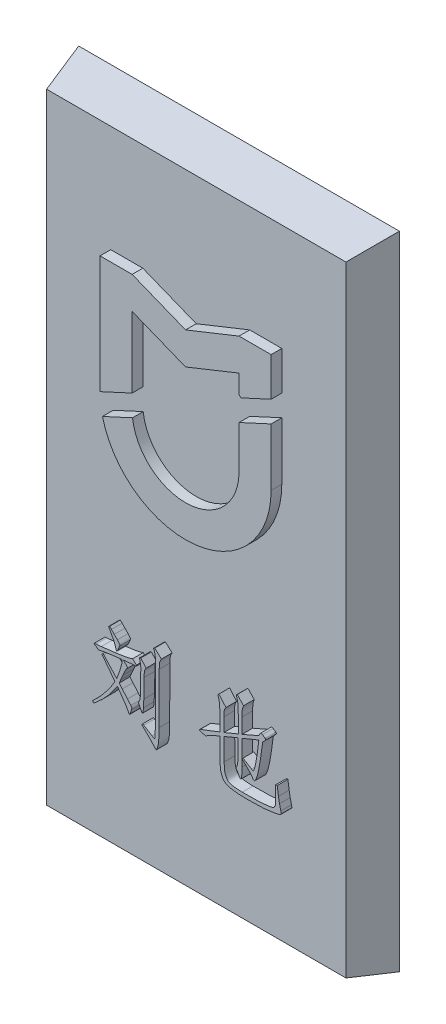
SolidWorks part; units mm, degrees
ref_plane "前视基准面" through (0, 0, 0) normal (0, 0, 1) x (1, 0, 0)
ref_plane "上视基准面" through (0, 0, 0) normal (0, 1, 0) x (1, 0, 0)
ref_plane "右视基准面" through (0, 0, 0) normal (1, 0, 0) x (0, 0, -1)
other "Configuration Table"
sketch "草图1" plane through (0, 0, 0) normal (0, 0, 1) x (1, 0, 0)
  line L18 (-15, -30) -> (15, -30)
  line L19 (-15, -30) -> (-15, 30)
  line L20 (-15, 30) -> (15, 30)
  line L21 (15, -30) -> (15, 30)
  line L22 (-15, -30) -> (15, 30) construction
  line L23 (-15, 30) -> (15, -30) construction
  point P0 (0, 0)
  dimension "D2" = 60
  dimension "D1" = 30
ref_plane "基准面1" through (0, 0, 4) normal (0, 0, 1) x (1, 0, 0)
sketch "草图2" plane through (0, 0, 4) normal (0, 0, 1) x (1, 0, 0)
  line L0 (-15, 30) -> (15, 30) construction
  line L1 (-14, -29) -> (14, -29)
  line L2 (-14, -29) -> (-14, 29)
  line L3 (-14, 29) -> (14, 29)
  line L4 (14, -29) -> (14, 29)
  line L5 (-14, -29) -> (14, 29) construction
  line L6 (-14, 29) -> (14, -29) construction
  line L7 (15, -30) -> (15, 30) construction
  point P0 (0, 0)
  dimension "D1" = 1
  dimension "D2" = 1
loft "放样1" add profiles "草图1", "草图2" connector at (-15, -30, 0) connector at (-14, -29, 4)
sketch "草图3" plane through (0, 0, 4) normal (0, 0, 1) x (1, 0, 0)
  line L0 (69.5095, 236.7647) -> (402.8428, 236.7647) construction
  line L1 (0, 3) -> (0, 0)
  line L2 (0, 0) -> (0, 41.0504) construction
  line L3 (-8, 8) -> (-8, 19)
  line L4 (-8, 19) -> (-5, 19)
  line L5 (-5, 19) -> (0, 17)
  line L6 (0, 17) -> (5, 19)
  line L7 (5, 19) -> (8, 19)
  line L8 (8, 19) -> (8, 15.3846)
  line L9 (8, 15.3846) -> (5, 14)
  line L10 (5, 14) -> (5, 16)
  line L11 (5, 16) -> (0, 14)
  line L12 (0, 14) -> (-5, 16)
  line L13 (-5, 16) -> (-5, 9.3846)
  line L14 (-5, 9.3846) -> (-8, 8)
  line L16 (5, 12) -> (8, 13.3846)
  line L19 (14, 29) -> (-14, 29) construction
  line L20 (8, 13.3846) -> (8, 8)
  line L21 (5, 12) -> (5, 8)
  line L22 (-4.964, 7.4012) -> (-7.7723, 6.1051)
  circle A0 centre (0, 8) radius 5
  circle A1 centre (0, 8) radius 8
  dimension "D1" = 5
  dimension "D2" = 15
  dimension "D3" = 2
  dimension "D4" = 3
  dimension "D5" = 2
  dimension "D6" = 3
  dimension "D7" = 6
extrude "凸台-拉伸2" add sketch "草图3" along normal blind 1 contours A1 L13 L12 L11 L10 L9 L8 L7 L6 L5 L4 L3 | L13 A1 L14 | A1 L16 L21 A0 L1 | A1 L20 L16 | L22 A1 L1 A0 | L11 A1 L12 region at (4.7825, 5.4619, 4) region at (-3.8597, 3.2925, 4) region at (7.5427, 11.7987, 4) region at (-6.2636, 10.7836, 4) region at (-0.9087, 16.3999, 4) region at (0, 15.168, 4)
sketch "草图4" plane through (0, 0, 4) normal (0, 0, 1) x (1, 0, 0)
  line L6 (-14, -17) -> (14, -17) construction
  line L7 (-14, -29) -> (-14, 29) construction
  line L8 (14, -29) -> (14, 29) construction
  text T0 "刘也" font "汉仪长仿宋体" height 6
  dimension "D1" = 17
extrude "凸台-拉伸3" add sketch "草图4" along normal blind 1
sketch "草图5" plane through (0, 0, 0) normal (0, 0, -1) x (-1, 0, 0)
  line L3 (15, -30) -> (-15, -30) construction
  line L4 (0, 18) -> (0, 0) construction
  line L5 (0, 0) -> (0, -18) construction
  circle A5 centre (0, 18) radius 5.5
  circle A6 centre (0, -18) radius 5.5
  circle A7 centre (0, 0) radius 5.5
  dimension "D5" = 12
  dimension "D1" = 11
extrude "切除-拉伸1" cut sketch "草图5" against normal blind 2
sketch "草图7" plane through (0, 0, 4) normal (0, 0, 1) x (1, 0, 0)
  line L0 (3.2108, -13.9623) -> (1.3838, -14.6693) construction
  line L1 (1.3838, -14.8163) -> (1.8889, -14.9544) construction
  line L2 (3.2223, -14.2896) -> (3.2338, -16.284) construction
  line L3 (8.9065, -17.5088) -> (8.7864, -16.9911) construction
  line L4 (8.7864, -16.9911) -> (8.6892, -16.4387) construction
  line L5 (8.6892, -16.4387) -> (8.569, -15.6192) construction
  line L6 (8.569, -15.6192) -> (8.4258, -15.6358) construction
  line L7 (8.4258, -15.6358) -> (8.413, -17.2071) construction
  line L8 (3.6072, -16.1882) -> (3.5944, -14.1349) construction
  line L9 (3.5944, -14.1349) -> (4.9163, -13.5826) construction
  line L10 (4.9163, -13.5826) -> (4.9163, -14.7997) construction
  line L11 (4.832, -16.3186) -> (4.9892, -16.6024) construction
  line L12 (5.2654, -15.7918) -> (5.2654, -13.4445) construction
  line L13 (5.2654, -13.4445) -> (6.8507, -12.7976) construction
  line L14 (6.1782, -15.4901) -> (5.3728, -14.9979) construction
  line L15 (5.3728, -14.9979) -> (5.3012, -15.127) construction
  line L16 (5.3012, -15.127) -> (5.6131, -15.4211) construction
  line L17 (5.6131, -15.4211) -> (5.9737, -15.7918) construction
  line L18 (5.9737, -15.7918) -> (6.2984, -16.1971) construction
  line L19 (7.4401, -12.3744) -> (7.1882, -12.1839) construction
  line L20 (7.0195, -12.1583) -> (6.8277, -12.4524) construction
  line L21 (6.8277, -12.4524) -> (5.2769, -13.1249) construction
  line L22 (5.2769, -13.1249) -> (5.2769, -11.7185) construction
  line L23 (5.4214, -10.7341) -> (4.832, -10.1127) construction
  line L24 (4.832, -10.1127) -> (4.7361, -10.1997) construction
  line L25 (4.9291, -11.753) -> (4.9291, -13.2629) construction
  line L26 (4.9291, -13.2629) -> (3.5829, -13.8242) construction
  line L27 (3.5829, -13.8242) -> (3.5829, -12.547) construction
  line L28 (3.7746, -11.7006) -> (3.1149, -10.9412) construction
  line L29 (3.1149, -10.9412) -> (3.0178, -11.0447) construction
  line L30 (3.2108, -12.3744) -> (3.2108, -13.9623) construction
  line L31 (-2.8861, -10.2163) -> (-2.9948, -10.2853) construction
  line L32 (-2.8017, -11.5459) -> (-2.826, -16.4822) construction
  line L33 (-3.138, -17.4488) -> (-3.9076, -16.9744) construction
  line L34 (-3.9076, -16.9744) -> (-4.0035, -16.9054) construction
  line L35 (-4.0035, -16.9054) -> (-4.0994, -17.0089) construction
  line L36 (-4.0994, -17.0089) -> (-3.9677, -17.1547) construction
  line L37 (-3.9677, -17.1547) -> (-3.3553, -17.7505) construction
  line L38 (-3.3553, -17.7505) -> (-2.9219, -18.2248) construction
  line L39 (-2.4898, -16.4643) -> (-2.4655, -11.7185) construction
  line L40 (-2.2609, -10.7954) -> (-2.8861, -10.2163) construction
  line L41 (-4.1838, -12.4434) -> (-4.1953, -12.8142) construction
  line L42 (-4.1953, -12.8142) -> (-4.2323, -14.6437) construction
  line L43 (-4.3525, -15.5323) -> (-4.2554, -15.7138) construction
  line L44 (-4.2554, -15.7138) -> (-4.148, -15.9209) construction
  line L45 (-3.9434, -15.5847) -> (-3.9076, -14.8598) construction
  line L46 (-3.9076, -14.8598) -> (-3.8718, -13.0814) construction
  line L47 (-3.6915, -12.2453) -> (-4.1953, -11.675) construction
  line L48 (-4.1953, -11.675) -> (-4.3154, -11.7275) construction
  line L49 (-8.702, -17.3887) -> (-8.6061, -17.5344) construction
  line L50 (-8.6061, -17.5344) -> (-8.4731, -17.4309) construction
  line L51 (-5.5658, -16.215) -> (-5.4214, -16.4822) construction
  line L52 (-5.4214, -16.4822) -> (-5.3255, -16.6638) construction
  line L53 (-5.1695, -16.6638) -> (-5.0608, -16.2917) construction
  line L54 (-5.1209, -15.9734) -> (-5.4341, -15.6103) construction
  line L55 (-5.4341, -15.6103) -> (-5.9264, -15.049) construction
  line L56 (-5.9264, -15.049) -> (-6.214, -14.7128) construction
  line L57 (-6.214, -14.7128) -> (-6.0823, -14.411) construction
  line L58 (-6.0823, -14.411) -> (-5.8535, -13.8932) construction
  line L59 (-5.4098, -13.0993) -> (-5.7934, -12.6505) construction
  line L60 (-5.7934, -12.6505) -> (-5.1938, -12.5905) construction
  line L61 (-5.1938, -12.5905) -> (-4.6287, -12.547) construction
  line L62 (-4.5929, -12.4434) -> (-4.9649, -12.1238) construction
  line L63 (-7.885, -12.5905) -> (-8.3657, -12.625) construction
  line L64 (-8.4859, -12.7452) -> (-8.2328, -12.9356) construction
  line L65 (-8.2328, -12.9356) -> (-8.1612, -12.9957) construction
  line L66 (-8.1612, -12.9957) -> (-7.9566, -12.9523) construction
  line L67 (-7.9566, -12.9523) -> (-7.4516, -12.8577) construction
  line L68 (-7.4516, -12.8577) -> (-6.9722, -12.7886) construction
  line L69 (-6.9722, -12.7886) -> (-5.9506, -12.6672) construction
  line L70 (-5.9506, -12.6672) -> (-5.9506, -12.8577) construction
  line L71 (-7.6447, -13.1594) -> (-7.729, -13.0737) construction
  line L72 (-7.729, -13.0737) -> (-7.8249, -13.1773) construction
  line L73 (-7.8249, -13.1773) -> (-7.729, -13.3064) construction
  line L74 (-8.6176, -17.3017) -> (-8.702, -17.3887) construction
  line L75 (-7.2113, -10.6305) -> (-7.1154, -10.7775) construction
  line L76 (-6.9722, -11.0537) -> (-6.8034, -11.3554) construction
  line L77 (-6.5273, -12.0292) -> (-6.503, -12.1149) construction
  line L78 (-6.3112, -12.0292) -> (-6.191, -11.7185) construction
  line L79 (-6.3828, -11.2953) -> (-6.6717, -10.9936) construction
  line L80 (-6.6717, -10.9936) -> (-6.9351, -10.7264) construction
  line L81 (-6.9351, -10.7264) -> (-7.1039, -10.5538) construction
  line L82 (-7.1039, -10.5538) -> (-7.2113, -10.6305) construction
  line L83 (3.2108, -13.9623) -> (1.3838, -14.6693)
  line L84 (1.3838, -14.8163) -> (1.8889, -14.9544)
  line L85 (3.2223, -14.2896) -> (3.2338, -16.284)
  line L86 (8.9065, -17.5088) -> (8.7864, -16.9911)
  line L87 (8.7864, -16.9911) -> (8.6892, -16.4387)
  line L88 (8.6892, -16.4387) -> (8.569, -15.6192)
  line L89 (8.569, -15.6192) -> (8.4258, -15.6358)
  line L90 (8.4258, -15.6358) -> (8.413, -17.2071)
  line L91 (3.6072, -16.1882) -> (3.5944, -14.1349)
  line L92 (3.5944, -14.1349) -> (4.9163, -13.5826)
  line L93 (4.9163, -13.5826) -> (4.9163, -14.7997)
  line L94 (4.832, -16.3186) -> (4.9892, -16.6024)
  line L95 (5.2654, -15.7918) -> (5.2654, -13.4445)
  line L96 (5.2654, -13.4445) -> (6.8507, -12.7976)
  line L97 (6.1782, -15.4901) -> (5.3728, -14.9979)
  line L98 (5.3728, -14.9979) -> (5.3012, -15.127)
  line L99 (5.3012, -15.127) -> (5.6131, -15.4211)
  line L100 (5.6131, -15.4211) -> (5.9737, -15.7918)
  line L101 (5.9737, -15.7918) -> (6.2984, -16.1971)
  line L102 (7.4401, -12.3744) -> (7.1882, -12.1839)
  line L103 (7.0195, -12.1583) -> (6.8277, -12.4524)
  line L104 (6.8277, -12.4524) -> (5.2769, -13.1249)
  line L105 (5.2769, -13.1249) -> (5.2769, -11.7185)
  line L106 (5.4214, -10.7341) -> (4.832, -10.1127)
  line L107 (4.832, -10.1127) -> (4.7361, -10.1997)
  line L108 (4.9291, -11.753) -> (4.9291, -13.2629)
  line L109 (4.9291, -13.2629) -> (3.5829, -13.8242)
  line L110 (3.5829, -13.8242) -> (3.5829, -12.547)
  line L111 (3.7746, -11.7006) -> (3.1149, -10.9412)
  line L112 (3.1149, -10.9412) -> (3.0178, -11.0447)
  line L113 (3.2108, -12.3744) -> (3.2108, -13.9623)
  line L114 (-2.8861, -10.2163) -> (-2.9948, -10.2853)
  line L115 (-2.8017, -11.5459) -> (-2.826, -16.4822)
  line L116 (-3.138, -17.4488) -> (-3.9076, -16.9744)
  line L117 (-3.9076, -16.9744) -> (-4.0035, -16.9054)
  line L118 (-4.0035, -16.9054) -> (-4.0994, -17.0089)
  line L119 (-4.0994, -17.0089) -> (-3.9677, -17.1547)
  line L120 (-3.9677, -17.1547) -> (-3.3553, -17.7505)
  line L121 (-3.3553, -17.7505) -> (-2.9219, -18.2248)
  line L122 (-2.4898, -16.4643) -> (-2.4655, -11.7185)
  line L123 (-2.2609, -10.7954) -> (-2.8861, -10.2163)
  line L124 (-4.1838, -12.4434) -> (-4.1953, -12.8142)
  line L125 (-4.1953, -12.8142) -> (-4.2323, -14.6437)
  line L126 (-4.3525, -15.5323) -> (-4.2554, -15.7138)
  line L127 (-4.2554, -15.7138) -> (-4.148, -15.9209)
  line L128 (-3.9434, -15.5847) -> (-3.9076, -14.8598)
  line L129 (-3.9076, -14.8598) -> (-3.8718, -13.0814)
  line L130 (-3.6915, -12.2453) -> (-4.1953, -11.675)
  line L131 (-4.1953, -11.675) -> (-4.3154, -11.7275)
  line L132 (-8.702, -17.3887) -> (-8.6061, -17.5344)
  line L133 (-8.6061, -17.5344) -> (-8.4731, -17.4309)
  line L134 (-5.5658, -16.215) -> (-5.4214, -16.4822)
  line L135 (-5.4214, -16.4822) -> (-5.3255, -16.6638)
  line L136 (-5.1695, -16.6638) -> (-5.0608, -16.2917)
  line L137 (-5.1209, -15.9734) -> (-5.4341, -15.6103)
  line L138 (-5.4341, -15.6103) -> (-5.9264, -15.049)
  line L139 (-5.9264, -15.049) -> (-6.214, -14.7128)
  line L140 (-6.214, -14.7128) -> (-6.0823, -14.411)
  line L141 (-6.0823, -14.411) -> (-5.8535, -13.8932)
  line L142 (-5.4098, -13.0993) -> (-5.7934, -12.6505)
  line L143 (-5.7934, -12.6505) -> (-5.1938, -12.5905)
  line L144 (-5.1938, -12.5905) -> (-4.6287, -12.547)
  line L145 (-4.5929, -12.4434) -> (-4.9649, -12.1238)
  line L146 (-7.885, -12.5905) -> (-8.3657, -12.625)
  line L147 (-8.4859, -12.7452) -> (-8.2328, -12.9356)
  line L148 (-8.2328, -12.9356) -> (-8.1612, -12.9957)
  line L149 (-8.1612, -12.9957) -> (-7.9566, -12.9523)
  line L150 (-7.9566, -12.9523) -> (-7.4516, -12.8577)
  line L151 (-7.4516, -12.8577) -> (-6.9722, -12.7886)
  line L152 (-6.9722, -12.7886) -> (-5.9506, -12.6672)
  line L153 (-5.9506, -12.6672) -> (-5.9506, -12.8577)
  line L154 (-7.6447, -13.1594) -> (-7.729, -13.0737)
  line L155 (-7.729, -13.0737) -> (-7.8249, -13.1773)
  line L156 (-7.8249, -13.1773) -> (-7.729, -13.3064)
  line L157 (-8.6176, -17.3017) -> (-8.702, -17.3887)
  line L158 (-7.2113, -10.6305) -> (-7.1154, -10.7775)
  line L159 (-6.9722, -11.0537) -> (-6.8034, -11.3554)
  line L160 (-6.5273, -12.0292) -> (-6.503, -12.1149)
  line L161 (-6.3112, -12.0292) -> (-6.191, -11.7185)
  line L162 (-6.3828, -11.2953) -> (-6.6717, -10.9936)
  line L163 (-6.6717, -10.9936) -> (-6.9351, -10.7264)
  line L164 (-6.9351, -10.7264) -> (-7.1039, -10.5538)
  line L165 (-7.1039, -10.5538) -> (-7.2113, -10.6305)
  spline S0 degree 3 poles (-1033.717, 1696.6076) (14.5849, -31.3392) (2.3796, -13.84) (1.322, -14.7057) (1.3032, -14.7272) (1.2978, -14.7519) (1.3028, -14.776) (1.3219, -14.7941) (2.4833, -15.4174) (10.8456, 3.4261) (-689.6183, -1891.6231) knots -16.626684 -16.626684 -16.626684 -16.626684 0.172084 0.308952 0.423314 0.521848 0.615174 0.717267 0.839241 17.04599 17.04599 17.04599 17.04599 only from (1.3838, -14.6693) to (1.3838, -14.8163) construction
  spline S1 degree 3 poles (-1193.4267, 1588.4483) (4.6942, -35.4098) (-2.0793, -17.6856) (2.0886, -14.8069) (2.1786, -14.7467) (2.255, -14.7057) (2.3236, -14.6723) (2.394, -14.6406) (2.4842, -14.6016) (2.5935, -14.5536) (2.723, -14.4991) (2.8716, -14.4348) (21.1798, -6.8784) (36.675, 7.0863) (846.5091, -1827.4773) knots -9.913111 -9.913111 -9.913111 -9.913111 0.088354 0.168711 0.240996 0.305231 0.342298 0.393919 0.460114 0.539323 0.633116 0.74183 0.864014 40.342075 40.342075 40.342075 40.342075 only from (1.8889, -14.9544) to (3.2223, -14.2896) construction
  spline S2 degree 3 poles (-1996.6425, -26.0924) (21.1619, -1.4114) (2.9373, -9.1514) (3.2408, -16.6481) (3.2493, -16.8011) (3.2608, -16.9395) (3.287, -17.0743) (3.3282, -17.2177) (3.3889, -17.3745) (3.4475, -17.514) (3.5093, -17.6275) (3.5725, -17.7068) (3.6497, -17.778) (3.7401, -17.842) (3.8439, -17.8993) (3.961, -17.9489) (4.091, -17.9913) (4.2346, -18.0246) (4.3907, -18.0542) (4.5598, -18.0774) (4.7413, -18.0999) (4.9353, -18.1162) (5.1417, -18.1268) (5.3603, -18.1366) (17.0583, -18.3013) (28.6468, -3.9526) (45.2697, -2017.6338) knots -5.726077 -5.726077 -5.726077 -5.726077 0.051298 0.096629 0.136668 0.171139 0.205044 0.243843 0.287585 0.336355 0.362012 0.388335 0.415202 0.443856 0.474721 0.507699 0.543092 0.581467 0.622821 0.667242 0.714879 0.765695 0.819407 0.876414 0.936712 9.962298 9.962298 9.962298 9.962298 only from (3.2338, -16.284) to (5.8305, -18.1391) construction
  spline S3 degree 3 poles (-13.558, -2017.9262) (-16.1126, -3.2156) (-4.8916, -18.3162) (6.2967, -18.1363) (6.5077, -18.135) (6.702, -18.1289) (6.8797, -18.1244) (7.0413, -18.1179) (7.1862, -18.1106) (7.3593, -18.0983) (7.5693, -18.079) (7.8251, -18.0454) (8.0919, -18.0098) (8.3171, -17.9718) (8.4924, -17.939) (8.6085, -17.9125) (8.7077, -17.8849) (8.7894, -17.8553) (8.8564, -17.8272) (8.9046, -17.795) (9.7801, -17.0547) (-10.3073, -3.2872) (1708.116, -1071.7951) knots -10.275083 -10.275083 -10.275083 -10.275083 0.076298 0.147407 0.213324 0.274064 0.329613 0.379985 0.425587 0.465631 0.542665 0.62318 0.707468 0.794943 0.837249 0.874555 0.906545 0.933712 0.95606 0.97423 0.988354 1.993762 1.993762 1.993762 1.993762 only from (5.8305, -18.1391) to (8.9538, -17.7249) construction
  spline S4 degree 3 poles (1950.4824, 462.1548) (-3.6389, -24.2841) (9.4886, -19.2587) (8.928, -17.6283) (8.3828, -15.5017) (24.8318, -10.629) (-1966.0478, -332.6785) knots -22.527171 -22.527171 -22.527171 -22.527171 0.152758 0.441236 0.761695 29.779876 29.779876 29.779876 29.779876 only from (8.9538, -17.7249) to (8.9065, -17.5088) construction
  spline S5 degree 3 poles (1964.363, -433.7342) (-12.5579, -7.9686) (9.2006, -15.0961) (8.374, -17.3632) (8.3303, -17.4427) (8.2869, -17.5147) (8.228, -17.5691) (8.157, -17.6037) (8.0635, -17.637) (7.9458, -17.6647) (7.8043, -17.6919) (7.6382, -17.714) (7.4476, -17.7331) (7.1586, -17.7525) (6.7742, -17.7729) (6.2972, -17.7876) (-12.0936, -18.089) (-30.4237, 1.2715) (-38.3924, -2017.04) knots -2.060584 -2.060584 -2.060584 -2.060584 0.022746 0.046909 0.073942 0.103777 0.121266 0.144564 0.173661 0.209707 0.252274 0.302159 0.35908 0.423101 0.560508 0.702361 0.848718 16.964876 16.964876 16.964876 16.964876 only from (8.413, -17.2071) to (5.3012, -17.7939) construction
  spline S6 degree 3 poles (-46.7827, -2016.9641) (22.8077, 5.2469) (13.3561, -18.3583) (4.7621, -17.7744) (4.5344, -17.7516) (4.3394, -17.7124) (4.1743, -17.6679) (4.0418, -17.6087) (3.9373, -17.5417) (3.8494, -17.4317) (3.7799, -17.2879) (3.7089, -17.1204) (3.6584, -16.9548) (3.628, -16.7397) (3.0291, -6.34) (22.0683, 4.4844) (-1996.1462, -34.556) knots -8.866171 -8.866171 -8.866171 -8.866171 0.102703 0.194721 0.275299 0.345385 0.405658 0.456275 0.49919 0.535795 0.603996 0.668093 0.728927 0.787086 0.898182 11.780137 11.780137 11.780137 11.780137 only from (5.3012, -17.7939) to (3.6072, -16.1882) construction
  spline S7 degree 3 poles (2004.3322, 28.2132) (-5.4357, 8.8885) (4.9939, -3.0766) (4.9157, -15.1159) (4.913, -15.2229) (4.9105, -15.3009) (4.9062, -15.3675) (4.8976, -15.4411) (4.8881, -15.5311) (4.8742, -15.6326) (4.8595, -15.7344) (4.8403, -15.8267) (4.8184, -15.904) (4.7924, -15.9663) (4.7664, -16.0149) (4.7485, -16.0553) (4.7377, -16.0864) (4.7267, -16.1124) (4.7369, -16.1442) (4.7545, -16.1874) (8.4419, -22.4311) (7.4888, -21.5343) (1094.0182, -1693.6924) knots -22.721442 -22.721442 -22.721442 -22.721442 0.117235 0.209236 0.277643 0.321637 0.358354 0.405016 0.463185 0.53135 0.600551 0.659631 0.71141 0.753745 0.788334 0.81677 0.837638 0.852065 0.86867 0.898605 0.942334 14.623876 14.623876 14.623876 14.623876 only from (4.9163, -14.7997) to (4.832, -16.3186) construction
  spline S8 degree 3 poles (-1550.7197, -1273.4139) (19.3456, 2.9931) (3.2309, -14.1918) (5.0799, -16.7505) (5.7712, -17.6613) (19.4263, 1.9782) (-1061.0354, -1708.7198) knots -34.275912 -34.275912 -34.275912 -34.275912 0.381659 0.667499 0.869536 12.383747 12.383747 12.383747 12.383747 only from (4.9892, -16.6024) to (5.1567, -16.8095) construction
  spline S9 degree 3 poles (918.7555, -1795.635) (-5.5243, 1.4675) (4.8071, -17.3305) (5.1958, -16.7827) (5.2129, -16.7483) (5.2282, -16.7063) (5.2394, -16.6557) (5.2459, -16.5944) (5.2522, -16.5121) (5.257, -16.4089) (5.2608, -16.2845) (5.2627, -16.1391) (5.4392, -7.5851) (-9.7444, 1.0472) (2005.1553, -7.1429) knots -1.687714 -1.687714 -1.687714 -1.687714 0.017456 0.042472 0.079552 0.130072 0.168818 0.227795 0.306061 0.404936 0.523255 0.662264 0.820778 24.999128 24.999128 24.999128 24.999128 only from (5.1567, -16.8095) to (5.2654, -15.7918) construction
  spline S10 degree 3 poles (1999.4433, -182.4933) (-0.9536, 17.1275) (8.3501, 1.4035) (6.8086, -13.2123) (6.7917, -13.371) (6.7732, -13.5025) (6.7549, -13.6268) (6.7362, -13.7638) (6.7125, -13.9226) (6.6791, -14.1669) (6.6279, -14.4944) (6.5596, -14.8224) (6.5056, -15.0718) (6.4665, -15.2245) (6.4351, -15.3421) (6.405, -15.4266) (6.3778, -15.4844) (6.3562, -15.5253) (6.3378, -15.5519) (6.3166, -15.5656) (6.2921, -15.5599) (6.2639, -15.5443) (4.0424, -14.2877) (11.2127, 0.4883) (-1139.8748, -1654.3969) knots -14.529546 -14.529546 -14.529546 -14.529546 0.077669 0.143357 0.196643 0.237586 0.276416 0.322552 0.376056 0.437289 0.569617 0.708128 0.772877 0.82528 0.866104 0.894742 0.914992 0.930089 0.941025 0.94733 0.953792 0.964678 0.979985 3.500837 3.500837 3.500837 3.500837 only from (6.8507, -12.7976) to (6.1782, -15.4901) construction
  spline S11 degree 3 poles (-1459.7871, -1376.4789) (16.124, -1.0165) (4.8212, -14.6345) (6.361, -16.2729) (7.1105, -16.8641) (15.6434, 1.6427) (-747.2579, -1868.7131) knots -40.720986 -40.720986 -40.720986 -40.720986 0.346655 0.629517 0.83833 17.401909 17.401909 17.401909 17.401909 only from (6.2984, -16.1971) to (6.4186, -16.3007) construction
  spline S12 degree 3 poles (837.9651, -1835.1249) (-8.1419, 10.6055) (5.776, -17.2113) (6.5025, -16.2565) (6.528, -16.2095) (6.5563, -16.1512) (6.5901, -16.0734) (6.631, -15.9775) (6.6736, -15.8661) (6.7146, -15.7421) (6.7515, -15.6071) (6.7856, -15.4601) (6.8204, -15.2999) (6.8542, -15.124) (6.8917, -14.9328) (6.9306, -14.7215) (6.9732, -14.4828) (7.0122, -14.2083) (7.0571, -13.8958) (7.0902, -13.6158) (7.1179, -13.389) (7.1385, -13.2361) (7.1567, -13.1048) (7.1715, -12.9952) (7.1853, -12.9069) (7.1977, -12.8407) (7.2081, -12.7966) (7.217, -12.763) (7.2413, -12.7362) (7.2737, -12.7029) (7.3166, -12.6607) (7.3686, -12.617) (7.4169, -12.5708) (7.4586, -12.5329) (7.4821, -12.4989) (7.4993, -12.4634) (7.0362, -10.9223) (-17.6107, -31.0912) (1493.2118, 1326.3414) knots -0.749252 -0.749252 -0.749252 -0.749252 0.011116 0.024256 0.034759 0.050015 0.070334 0.09545 0.124469 0.15558 0.188759 0.224443 0.263394 0.305925 0.352459 0.40264 0.459525 0.525733 0.60077 0.685168 0.727217 0.76409 0.795449 0.821898 0.843179 0.859308 0.869947 0.875726 0.883767 0.895184 0.909185 0.926664 0.943691 0.957044 0.966676 0.973237 0.984469 2.007557 2.007557 2.007557 2.007557 only from (6.4186, -16.3007) to (7.4401, -12.3744) construction
  spline S13 degree 3 poles (902.0496, 1776.4099) (0.6886, -34.6242) (9.0767, -12.9356) (7.086, -12.1281) (6.1315, -12.1467) (19.65, -37.5566) (-984.4161, 1724.6464) knots -32.736634 -32.736634 -32.736634 -32.736634 0.367152 0.634154 0.821366 13.935133 13.935133 13.935133 13.935133 only from (7.1882, -12.1839) to (7.0195, -12.1583) construction
  spline S14 degree 3 poles (-1994.6009, 0.495) (23.7054, -26.4113) (4.9761, -18.7485) (5.2835, -11.3643) (5.2914, -11.232) (5.3038, -11.1262) (5.3257, -11.034) (5.3512, -10.9406) (6.9792, -5.8121) (22.7426, -5.6507) (-1877.5534, 663.1337) knots -21.608795 -21.608795 -21.608795 -21.608795 0.198899 0.364768 0.496393 0.59539 0.682927 0.77943 0.885076 16.774062 16.774062 16.774062 16.774062 only from (5.2769, -11.7185) to (5.4214, -10.7341) construction
  spline S15 degree 3 poles (1902.8334, 619.7227) (-16.1551, -6.6372) (3.4236, -5.5784) (4.816, -10.4468) (4.8463, -10.5591) (4.8758, -10.7012) (4.902, -10.8854) (4.9158, -11.0799) (4.9214, -11.254) (4.9279, -11.4048) (4.905, -22.6176) (16.3078, -33.5295) (-1993.4919, -88.7053) knots -9.399112 -9.399112 -9.399112 -9.399112 0.086759 0.167144 0.240968 0.308143 0.443474 0.594867 0.67934 0.775169 0.882309 22.030604 22.030604 22.030604 22.030604 only from (4.7361, -10.1997) to (4.9291, -11.753) construction
  spline S16 degree 3 poles (-1996.3066, -6.3279) (21.0986, -26.1786) (3.2376, -19.0978) (3.5925, -12.2086) (3.6071, -12.0674) (3.6279, -11.9648) (3.6579, -11.8939) (3.6875, -11.8361) (6.3076, -7.6291) (19.1276, -10.4641) (-1635.6374, 1133.6983) knots -22.753125 -22.753125 -22.753125 -22.753125 0.200316 0.389353 0.554689 0.680516 0.74126 0.814082 0.900083 17.48624 17.48624 17.48624 17.48624 only from (3.5829, -12.547) to (3.7746, -11.7006) construction
  spline S17 degree 3 poles (1903.9912, 610.2623) (-20.7158, -5.6325) (1.4769, -5.2348) (3.1267, -11.4022) (3.1599, -11.5753) (3.1876, -11.7958) (3.8456, -21.4883) (-18.235, -31.7664) (2002.9406, 15.7492) knots -13.754831 -13.754831 -13.754831 -13.754831 0.142454 0.27858 0.408689 0.533703 0.771853 21.965234 21.965234 21.965234 21.965234 only from (3.0178, -11.0447) to (3.2108, -12.3744) construction
  spline S18 degree 3 poles (1863.0803, 709.0915) (-22.3797, -4.1401) (-5.0305, -4.4694) (-2.8997, -10.5404) (-2.8683, -10.6465) (-2.844, -10.7698) (-2.829, -10.9212) (-2.8225, -11.0733) (-2.8168, -11.193) (-2.8154, -11.2703) (-2.8106, -11.3328) (-2.8079, -11.3968) (-2.5223, -14.669) (-19.2275, -18.627) (1995.8178, 61.3832) knots -14.7087 -14.7087 -14.7087 -14.7087 0.116167 0.216181 0.30306 0.374052 0.509134 0.657525 0.72919 0.788892 0.837713 0.875556 0.938334 8.497053 8.497053 8.497053 8.497053 only from (-2.9948, -10.2853) to (-2.8017, -11.5459) construction
  spline S19 degree 3 poles (1996.6884, -57.1725) (-15.54, -4.2723) (-2.5643, -10.6635) (-2.8326, -16.6987) (-2.8349, -16.7929) (-2.8368, -16.8769) (-2.8416, -16.9497) (-2.8431, -17.0124) (-2.8477, -17.0639) (-2.8518, -17.1377) (-2.8594, -17.2275) (-2.8586, -17.3285) (-2.6706, -19.1698) (-24.0229, -19.8512) (1993.9836, -127.1361) knots -18.086944 -18.086944 -18.086944 -18.086944 0.116901 0.223456 0.319585 0.404033 0.479451 0.541837 0.595221 0.636857 0.766948 0.869544 0.944906 6.362298 6.362298 6.362298 6.362298 only from (-2.826, -16.4822) to (-2.8618, -17.4654) construction
  spline S20 degree 3 poles (1920.7346, -564.8783) (-19.9028, -9.0246) (-2.2232, -15.9139) (-2.8844, -17.541) (-2.8944, -17.5636) (-2.9124, -17.5786) (-2.943, -17.5624) (-2.9871, -17.5419) (-7.9881, -14.4729) (-0.924, -15.4233) (-1899.5268, 617.8288) knots -13.418067 -13.418067 -13.418067 -13.418067 0.123946 0.216991 0.278308 0.31908 0.381479 0.515917 0.721003 45.525651 45.525651 45.525651 45.525651 only from (-2.8618, -17.4654) to (-3.138, -17.4488) construction
  spline S21 degree 3 poles (194.9213, -2008.3902) (-15.0275, 1.5883) (-8.4676, -12.6222) (-2.8057, -18.3428) (-2.0182, -19.0945) (7.0662, -6.6445) (-1066.911, -1711.4586) knots -97.933846 -97.933846 -97.933846 -97.933846 0.408799 0.710783 0.906834 13.513962 13.513962 13.513962 13.513962 only from (-2.9219, -18.2248) to (-2.7416, -18.3897) construction
  spline S22 degree 3 poles (1541.3019, -1289.3663) (-17.2182, -8.6749) (-3.0151, -19.2135) (-2.6957, -18.315) (-2.6594, -18.2339) (-2.6181, -18.1202) (-2.5776, -17.9866) (-2.5431, -17.8417) (-2.5239, -17.6904) (-2.5098, -17.4826) (-2.5022, -17.2234) (-2.497, -16.9689) (-2.4939, -16.7788) (-2.491, -16.6565) (-2.4063, -10.64) (-11.8864, -4.6267) (1997.4337, -6.5983) knots -1.306783 -1.306783 -1.306783 -1.306783 0.011073 0.038994 0.08476 0.148534 0.222584 0.297979 0.375406 0.454948 0.615659 0.771094 0.84328 0.905715 0.957736 10.02345 10.02345 10.02345 10.02345 only from (-2.7416, -18.3897) to (-2.4898, -16.4643) construction
  spline S23 degree 3 poles (-2002.0433, 23.4082) (17.2178, -26.8655) (-2.9385, -18.8244) (-2.4518, -11.3454) (-2.4395, -11.2317) (-2.4299, -11.1629) (-2.4183, -11.1079) (-2.4062, -11.0612) (-2.3851, -11.014) (-2.3537, -10.9557) (0.2121, -6.3458) (14.755, -8.7652) (-1720.7414, 1012.1287) knots -22.788299 -22.788299 -22.788299 -22.788299 0.226747 0.424712 0.510059 0.582424 0.640662 0.684729 0.732249 0.801029 0.890645 17.139984 17.139984 17.139984 17.139984 only from (-2.4655, -11.7185) to (-2.2609, -10.7954) construction
  spline S24 degree 3 poles (1924.5555, 516.4873) (-21.4595, -4.1063) (-5.6484, -6.1098) (-4.2553, -11.9618) (-4.2351, -12.066) (-4.2157, -12.1849) (-3.2666, -19.1695) (-14.338, -27.5253) (1984.5585, 198.7689) knots -24.265145 -24.265145 -24.265145 -24.265145 0.176124 0.336499 0.483023 0.612769 0.832275 29.485687 29.485687 29.485687 29.485687 only from (-4.3154, -11.7275) to (-4.1838, -12.4434) construction
  spline S25 degree 3 poles (1993.4071, -111.1275) (-26.4009, -2.323) (-3.6574, -9.2924) (-4.2529, -14.9872) (-4.2827, -15.1305) (-4.3269, -15.2317) (-4.3657, -15.2981) (-4.3838, -15.3404) (-4.396, -15.3739) (-4.4028, -15.4128) (-3.7015, -17.7808) (17.82, -6.713) (-1681.3534, -1105.1804) knots -18.0051 -18.0051 -18.0051 -18.0051 0.201752 0.379581 0.534025 0.67384 0.735013 0.783251 0.822556 0.850486 0.909807 8.568288 8.568288 8.568288 8.568288 only from (-4.2323, -14.6437) to (-4.3525, -15.5323) construction
  spline S26 degree 3 poles (-1512.9602, -1328.6343) (10.4966, 3.2816) (-5.5522, -14.0466) (-4.0797, -16.0348) (-4.0465, -16.064) (-4.0156, -16.055) (-4.0025, -16.0314) (-3.9917, -16.0026) (-3.9815, -15.9618) (-3.9734, -15.9091) (-3.9642, -15.8448) (-3.9571, -15.7684) (-3.4918, -10.72) (-16.7031, -4.6524) (1991.2791, -152.9923) knots -10.887367 -10.887367 -10.887367 -10.887367 0.121964 0.207693 0.260892 0.300142 0.329863 0.376288 0.436469 0.514652 0.611416 0.722891 0.853081 22.971798 22.971798 22.971798 22.971798 only from (-4.148, -15.9209) to (-3.9434, -15.5847) construction
  spline S27 degree 3 poles (1994.0865, -101.0049) (-13.6723, -29.9635) (-3.8891, -21.5767) (-3.8702, -12.858) (-3.866, -12.7715) (-3.86, -12.6843) (-3.8474, -12.597) (-3.8347, -12.516) (-3.8137, -12.4521) (-3.7836, -12.3943) (-1.8693, -9.0083) (15.3369, -14.8877) (-1709.4277, 1031.8458) knots -29.538415 -29.538415 -29.538415 -29.538415 0.141799 0.263135 0.361172 0.438866 0.562703 0.663904 0.719374 0.792594 0.886876 14.061788 14.061788 14.061788 14.061788 only from (-3.8718, -13.0814) to (-3.6915, -12.2453) construction
  spline S28 degree 3 poles (1264.9967, -1559.4891) (-31.5873, -12.0786) (-13.6284, -22.0641) (-8.1342, -17.1422) (-7.9369, -16.9598) (-7.7283, -16.7545) (-7.5206, -16.5461) (-7.3343, -16.3462) (-7.1732, -16.1672) (-7.0581, -16.0237) (-6.9736, -15.91) (-6.9052, -15.8183) (-6.8336, -15.7144) (-6.7531, -15.6022) (-6.67, -15.4779) (-6.5781, -15.3451) (2.1562, -2.044) (17.435, 6.7071) (-1628.834, 1154.0726) knots -6.726074 -6.726074 -6.726074 -6.726074 0.062764 0.136145 0.220514 0.315903 0.411855 0.497633 0.57328 0.638674 0.670791 0.706683 0.746446 0.789663 0.836764 0.887318 0.941766 15.825984 15.825984 15.825984 15.825984 only from (-8.4731, -17.4309) to (-6.3828, -15.049) construction
  spline S29 degree 3 poles (-1774.7239, -949.3367) (-0.7487, -7.6484) (-7.3553, -13.3952) (-6.347, -15.1129) (-6.313, -15.1624) (-6.2693, -15.2266) (-6.2164, -15.3059) (-6.1504, -15.3976) (-6.0752, -15.5038) (-5.9929, -15.6196) (-5.909, -15.7352) (-5.8309, -15.8422) (-5.7637, -15.9368) (-5.7051, -16.0177) (-5.6581, -16.0866) (-5.617, -16.1403) (-2.5499, -20.6038) (-3.1453, -27.2731) (1710.5712, 1010.7307) knots -4.10249 -4.10249 -4.10249 -4.10249 0.017268 0.047445 0.089524 0.143804 0.211032 0.29024 0.381658 0.485286 0.589437 0.682632 0.764344 0.833847 0.893123 0.939986 0.976096 12.299151 12.299151 12.299151 12.299151 only from (-6.3828, -15.049) to (-5.5658, -16.215) construction
  spline S30 degree 3 poles (-1652.1034, -1151.5707) (8.8374, -2.9824) (-6.3284, -15.4657) (-5.2823, -16.7295) (-5.2616, -16.749) (-5.239, -16.7551) (-5.2169, -16.7491) (-5.1987, -16.7299) (-4.4002, -15.3061) (-20.3074, -6.3517) (1819.6509, -834.9933) knots -19.315907 -19.315907 -19.315907 -19.315907 0.184014 0.329932 0.435758 0.52042 0.60011 0.698183 0.82936 20.217518 20.217518 20.217518 20.217518 only from (-5.3255, -16.6638) to (-5.1695, -16.6638) construction
  spline S31 degree 3 poles (1756.3388, -963.5015) (-15.7851, -19.7388) (-6.0338, -20.2901) (-5.0347, -16.1894) (-5.0317, -16.153) (-5.0297, -16.1236) (-5.0402, -16.096) (-5.057, -16.0623) (-7.8026, -12.1779) (-16.0197, -15.5805) (1187.0566, 1589.806) knots -35.897109 -35.897109 -35.897109 -35.897109 0.175028 0.3144 0.421741 0.491694 0.565052 0.672076 0.818098 41.504706 41.504706 41.504706 41.504706 only from (-5.0608, -16.2917) to (-5.1209, -15.9734) construction
  spline S32 degree 3 poles (-1844.512, 772.8216) (-1.9985, -31.3954) (-8.803, -20.3942) (-5.7663, -13.6971) (-5.7298, -13.6114) (-5.6969, -13.5363) (-5.6669, -13.4717) (-5.6414, -13.4167) (-5.62, -13.3716) (-5.5873, -13.3017) (-3.5534, -10.1993) (22.2359, -28.7518) (-1476.7841, 1341.5083) knots -23.688236 -23.688236 -23.688236 -23.688236 0.124711 0.237544 0.339212 0.428998 0.50564 0.571681 0.627122 0.668853 0.823736 12.607364 12.607364 12.607364 12.607364 only from (-5.8535, -13.8932) to (-5.4098, -13.0993) construction
  spline S33 degree 3 poles (1048.4675, -1712.7468) (-20.15, 9.6222) (-5.0308, -13.2656) (-4.5787, -12.5119) (-4.4352, -11.4786) (-31.1321, -16.4036) (1947.3773, 423.0108) knots -17.330031 -17.330031 -17.330031 -17.330031 0.228603 0.460739 0.719052 22.488112 22.488112 22.488112 22.488112 only from (-4.6287, -12.547) to (-4.5929, -12.4434) construction
  spline S34 degree 3 poles (617.1539, -1912.8033) (1.0615, 6.6518) (0.4277, -10.6214) (-5.2524, -12.2113) (-5.4248, -12.2495) (-5.6173, -12.2898) (-5.8305, -12.3277) (-6.0647, -12.3642) (-16.7545, -13.9589) (-29.7673, 2.3999) (227.2617, -1998.576) knots -10.40378 -10.40378 -10.40378 -10.40378 0.082838 0.177515 0.284544 0.402898 0.534005 0.677173 0.832565 20.129151 20.129151 20.129151 20.129151 only from (-4.9649, -12.1238) to (-6.5873, -12.4345) construction
  spline S35 degree 3 poles (298.0282, -1988.6784) (34.5431, 3.4816) (14.3568, -9.9504) (-7.256, -12.5157) (-26.2506, -14.8362) (-46.4544, -6.0355) (171.7781, -2004.1497) knots -49.192308 -49.192308 -49.192308 -49.192308 0.264132 0.518317 0.763645 44.186385 44.186385 44.186385 44.186385 only from (-6.5873, -12.4345) to (-7.885, -12.5905) construction
  spline S36 degree 3 poles (-1461.4057, 1361.6465) (11.9395, -25.8139) (-5.9466, -12.0262) (-8.5083, -12.6493) (-8.5576, -12.6619) (-8.5585, -12.6948) (-6.6522, -14.1057) (-12.4698, 0.822) (848.919, -1819.5851) knots -27.163084 -27.163084 -27.163084 -27.163084 0.274008 0.539418 0.638409 0.701183 0.813539 22.170768 22.170768 22.170768 22.170768 only from (-8.3657, -12.625) to (-8.4859, -12.7452) construction
  spline S37 degree 3 poles (1980.3886, -245.9002) (-25.6618, -4.0136) (-5.2924, -9.814) (-5.9842, -13.0963) (-6.0243, -13.2582) (-6.0787, -13.4503) (-6.1499, -13.6689) (-6.2318, -13.9123) (-11.99, -28.9406) (-30.0035, -38.8194) (1823.522, -820.849) knots -5.750981 -5.750981 -5.750981 -5.750981 0.058152 0.137295 0.236273 0.356767 0.494511 0.647688 0.816423 29.295179 29.295179 29.295179 29.295179 only from (-5.9506, -12.8577) to (-6.4429, -14.4545) construction
  spline S38 degree 3 poles (-1440.4806, -1408.4344) (12.2022, -13.7825) (-2.3288, -18.9321) (-6.635, -14.2521) (-6.7478, -14.1367) (-6.9051, -13.9638) (-7.1046, -13.7457) (-7.3024, -13.5363) (-7.4406, -13.3794) (-7.5273, -13.2883) (-11.1426, -9.2579) (-21.1289, -11.1301) (1455.1445, 1350.6897) knots -10.550678 -10.550678 -10.550678 -10.550678 0.072662 0.155077 0.246174 0.346541 0.551898 0.74801 0.835624 0.906789 0.961595 10.027963 10.027963 10.027963 10.027963 only from (-6.4429, -14.4545) to (-7.6447, -13.1594) construction
  spline S39 degree 3 poles (-1690.9874, -1093.1833) (3.3964, -3.003) (-8.5702, -12.3185) (-7.6792, -13.3782) (-7.6356, -13.4372) (-7.5827, -13.4978) (-7.5262, -13.5706) (-7.4574, -13.6543) (-7.3699, -13.7703) (-7.2605, -13.9156) (-7.1281, -14.0897) (-6.975, -14.2939) (4.9528, -30.4112) (25.9086, -39.6948) (-1573.915, -1256.6215) knots -2.148203 -2.148203 -2.148203 -2.148203 0.015763 0.043388 0.082758 0.134752 0.173579 0.232037 0.310356 0.408975 0.526794 0.664916 0.822376 33.019448 33.019448 33.019448 33.019448 only from (-7.729, -13.3064) to (-6.6116, -14.7818) construction
  spline S40 degree 3 poles (1720.3243, -1023.3234) (-16.1487, 18.5257) (-0.3829, -5.2401) (-7.063, -15.5177) (-7.2989, -15.8542) (-7.5036, -16.115) (-7.6664, -16.3087) (-7.7781, -16.444) (-7.8861, -16.5659) (-7.9856, -16.679) (-8.079, -16.7812) (-8.1654, -16.8734) (-8.2462, -16.9542) (-8.3206, -17.0243) (-8.3868, -17.0855) (-8.4452, -17.1383) (-8.4946, -17.184) (-8.5356, -17.2221) (-8.5675, -17.2534) (-8.5919, -17.2758) (-10.0031, -18.7121) (-13.9652, -17.5077) (1380.8721, -1455.6115) knots -10.967114 -10.967114 -10.967114 -10.967114 0.13677 0.268528 0.395276 0.51773 0.575816 0.629956 0.680367 0.726837 0.769636 0.808773 0.843982 0.87557 0.903536 0.927593 0.948568 0.965902 0.979597 0.98994 0.996647 2.846485 2.846485 2.846485 2.846485 only from (-6.6116, -14.7818) to (-8.6176, -17.3017) construction
  spline S41 degree 3 poles (-1863.6245, -754.3794) (4.4911, -3.082) (-7.7846, -9.5752) (-7.0741, -10.8691) (-4.3579, -16.0121) (12.1418, -14.6441) (-1809.0679, -878.3222) knots -13.550654 -13.550654 -13.550654 -13.550654 0.090846 0.287239 0.590215 56.191237 56.191237 56.191237 56.191237 only from (-7.1154, -10.7775) to (-6.9722, -11.0537) construction
  spline S42 degree 3 poles (1834.9168, 768.1255) (-43.4567, -10.4562) (24.5419, 1.0806) (-32.1871, -38.5399) (1852.1265, 726.1252) knots -30.614491 -30.614491 -30.614491 -30.614491 0.497436 31.719294 31.719294 31.719294 31.719294 only from (-6.8034, -11.3554) to (-6.5273, -12.0292) construction
  spline S43 degree 3 poles (-1865.1417, -750.4644) (10.0329, -1.5337) (-7.3015, -10.4965) (-6.4726, -12.1947) (-6.45, -12.2151) (-6.4207, -12.2124) (-6.395, -12.1889) (-6.3692, -12.1506) (-4.9295, -9.4946) (-20.1862, 0.6082) (1823.1195, -820.1308) knots -15.623058 -15.623058 -15.623058 -15.623058 0.147979 0.251119 0.323111 0.388004 0.477994 0.606878 0.779247 25.920813 25.920813 25.920813 25.920813 only from (-6.503, -12.1149) to (-6.3112, -12.0292) construction
  spline S44 degree 3 poles (-1912.8987, -615.0411) (10.2854, -11.3835) (-7.4086, -14.4578) (-6.1458, -11.6023) (-6.1514, -11.5735) (-6.1633, -11.5549) (-6.1798, -11.5283) (-6.2061, -11.4958) (-6.2388, -11.4549) (-6.28, -11.4078) (-12.3004, -4.7951) (-23.0878, -2.3486) (1486.2203, 1319.7709) knots -17.033327 -17.033327 -17.033327 -17.033327 0.164438 0.264555 0.289914 0.332187 0.391502 0.47307 0.575597 0.69724 0.838081 52.760377 52.760377 52.760377 52.760377 only from (-6.191, -11.7185) to (-6.3828, -11.2953) construction
  spline S45 degree 3 poles (1.3838, -14.6693) (1.3711, -14.6746) (1.3482, -14.6842) (1.322, -14.7057) (1.3032, -14.7272) (1.2978, -14.7519) (1.3028, -14.776) (1.3219, -14.7941) (1.3491, -14.8087) (1.3713, -14.8135) (1.3838, -14.8163) knots 0 0 0 0 0.172084 0.308952 0.423314 0.521848 0.615174 0.717267 0.839241 1 1 1 1
  spline S46 degree 3 poles (1.8889, -14.9544) (1.9235, -14.9272) (1.9897, -14.8752) (2.0886, -14.8069) (2.1786, -14.7467) (2.255, -14.7057) (2.3236, -14.6723) (2.394, -14.6406) (2.4842, -14.6016) (2.5935, -14.5536) (2.723, -14.4991) (2.8716, -14.4348) (3.0408, -14.365) (3.1597, -14.3156) (3.2223, -14.2896) knots 0 0 0 0 0.088354 0.168711 0.240996 0.305231 0.342298 0.393919 0.460114 0.539323 0.633116 0.74183 0.864014 1 1 1 1
  spline S47 degree 3 poles (3.2338, -16.284) (3.2338, -16.3497) (3.2337, -16.4733) (3.2408, -16.6481) (3.2493, -16.8011) (3.2608, -16.9395) (3.287, -17.0743) (3.3282, -17.2177) (3.3889, -17.3745) (3.4475, -17.514) (3.5093, -17.6275) (3.5725, -17.7068) (3.6497, -17.778) (3.7401, -17.842) (3.8439, -17.8993) (3.961, -17.9489) (4.091, -17.9913) (4.2346, -18.0246) (4.3907, -18.0542) (4.5598, -18.0774) (4.7413, -18.0999) (4.9353, -18.1162) (5.1417, -18.1268) (5.3603, -18.1366) (5.5914, -18.1398) (5.7495, -18.1394) (5.8305, -18.1391) knots 0 0 0 0 0.051298 0.096629 0.136668 0.171139 0.205044 0.243843 0.287585 0.336355 0.362012 0.388335 0.415202 0.443856 0.474721 0.507699 0.543092 0.581467 0.622821 0.667242 0.714879 0.765695 0.819407 0.876414 0.936712 1 1 1 1
  spline S48 degree 3 poles (5.8305, -18.1391) (5.9119, -18.1394) (6.0691, -18.1399) (6.2967, -18.1363) (6.5077, -18.135) (6.702, -18.1289) (6.8797, -18.1244) (7.0413, -18.1179) (7.1862, -18.1106) (7.3593, -18.0983) (7.5693, -18.079) (7.8251, -18.0454) (8.0919, -18.0098) (8.3171, -17.9718) (8.4924, -17.939) (8.6085, -17.9125) (8.7077, -17.8849) (8.7894, -17.8553) (8.8564, -17.8272) (8.9046, -17.795) (8.9417, -17.7637) (8.9501, -17.737) (8.9538, -17.7249) knots 0 0 0 0 0.076298 0.147407 0.213324 0.274064 0.329613 0.379985 0.425587 0.465631 0.542665 0.62318 0.707468 0.794943 0.837249 0.874555 0.906545 0.933712 0.95606 0.97423 0.988354 1 1 1 1
  spline S49 degree 3 poles (8.9538, -17.7249) (8.9519, -17.7138) (8.9463, -17.6816) (8.928, -17.6283) (8.9124, -17.5675) (8.9083, -17.5264) (8.9065, -17.5088) knots 0 0 0 0 0.152758 0.441236 0.761695 1 1 1 1
  spline S50 degree 3 poles (8.413, -17.2071) (8.4097, -17.2325) (8.4027, -17.2847) (8.374, -17.3632) (8.3303, -17.4427) (8.2869, -17.5147) (8.228, -17.5691) (8.157, -17.6037) (8.0635, -17.637) (7.9458, -17.6647) (7.8043, -17.6919) (7.6382, -17.714) (7.4476, -17.7331) (7.1586, -17.7525) (6.7742, -17.7729) (6.2972, -17.7876) (5.8045, -17.7956) (5.4708, -17.7945) (5.3012, -17.7939) knots 0 0 0 0 0.022746 0.046909 0.073942 0.103777 0.121266 0.144564 0.173661 0.209707 0.252274 0.302159 0.35908 0.423101 0.560508 0.702361 0.848718 1 1 1 1
  spline S51 degree 3 poles (5.3012, -17.7939) (5.2044, -17.7933) (5.0209, -17.792) (4.7621, -17.7744) (4.5344, -17.7516) (4.3394, -17.7124) (4.1743, -17.6679) (4.0418, -17.6087) (3.9373, -17.5417) (3.8494, -17.4317) (3.7799, -17.2879) (3.7089, -17.1204) (3.6584, -16.9548) (3.628, -16.7397) (3.6133, -16.4846) (3.6092, -16.2841) (3.6072, -16.1882) knots 0 0 0 0 0.102703 0.194721 0.275299 0.345385 0.405658 0.456275 0.49919 0.535795 0.603996 0.668093 0.728927 0.787086 0.898182 1 1 1 1
  spline S52 degree 3 poles (4.9163, -14.7997) (4.9164, -14.8611) (4.9166, -14.9706) (4.9157, -15.1159) (4.913, -15.2229) (4.9105, -15.3009) (4.9062, -15.3675) (4.8976, -15.4411) (4.8881, -15.5311) (4.8742, -15.6326) (4.8595, -15.7344) (4.8403, -15.8267) (4.8184, -15.904) (4.7924, -15.9663) (4.7664, -16.0149) (4.7485, -16.0553) (4.7377, -16.0864) (4.7267, -16.1124) (4.7369, -16.1442) (4.7545, -16.1874) (4.7897, -16.247) (4.8166, -16.2926) (4.832, -16.3186) knots 0 0 0 0 0.117235 0.209236 0.277643 0.321637 0.358354 0.405016 0.463185 0.53135 0.600551 0.659631 0.71141 0.753745 0.788334 0.81677 0.837638 0.852065 0.86867 0.898605 0.942334 1 1 1 1
  spline S53 degree 3 poles (4.9892, -16.6024) (5.0056, -16.6332) (5.0341, -16.6872) (5.0799, -16.7505) (5.1155, -16.7974) (5.1451, -16.8061) (5.1567, -16.8095) knots 0 0 0 0 0.381659 0.667499 0.869536 1 1 1 1
  spline S54 degree 3 poles (5.1567, -16.8095) (5.163, -16.8089) (5.1783, -16.8074) (5.1958, -16.7827) (5.2129, -16.7483) (5.2282, -16.7063) (5.2394, -16.6557) (5.2459, -16.5944) (5.2522, -16.5121) (5.257, -16.4089) (5.2608, -16.2845) (5.2627, -16.1391) (5.2662, -15.9725) (5.2657, -15.8545) (5.2654, -15.7918) knots 0 0 0 0 0.017456 0.042472 0.079552 0.130072 0.168818 0.227795 0.306061 0.404936 0.523255 0.662264 0.820778 1 1 1 1
  spline S55 degree 3 poles (6.8507, -12.7976) (6.8431, -12.8747) (6.8292, -13.0171) (6.8086, -13.2123) (6.7917, -13.371) (6.7732, -13.5025) (6.7549, -13.6268) (6.7362, -13.7638) (6.7125, -13.9226) (6.6791, -14.1669) (6.6279, -14.4944) (6.5596, -14.8224) (6.5056, -15.0718) (6.4665, -15.2245) (6.4351, -15.3421) (6.405, -15.4266) (6.3778, -15.4844) (6.3562, -15.5253) (6.3378, -15.5519) (6.3166, -15.5656) (6.2921, -15.5599) (6.2639, -15.5443) (6.2236, -15.5215) (6.1946, -15.5015) (6.1782, -15.4901) knots 0 0 0 0 0.077669 0.143357 0.196643 0.237586 0.276416 0.322552 0.376056 0.437289 0.569617 0.708128 0.772877 0.82528 0.866104 0.894742 0.914992 0.930089 0.941025 0.94733 0.953792 0.964678 0.979985 1 1 1 1
  spline S56 degree 3 poles (6.2984, -16.1971) (6.3096, -16.2123) (6.33, -16.2399) (6.361, -16.2729) (6.3897, -16.2956) (6.4098, -16.2991) (6.4186, -16.3007) knots 0 0 0 0 0.346655 0.629517 0.83833 1 1 1 1
  spline S57 degree 3 poles (6.4186, -16.3007) (6.4348, -16.3001) (6.4703, -16.2988) (6.5025, -16.2565) (6.528, -16.2095) (6.5563, -16.1512) (6.5901, -16.0734) (6.631, -15.9775) (6.6736, -15.8661) (6.7146, -15.7421) (6.7515, -15.6071) (6.7856, -15.4601) (6.8204, -15.2999) (6.8542, -15.124) (6.8917, -14.9328) (6.9306, -14.7215) (6.9732, -14.4828) (7.0122, -14.2083) (7.0571, -13.8958) (7.0902, -13.6158) (7.1179, -13.389) (7.1385, -13.2361) (7.1567, -13.1048) (7.1715, -12.9952) (7.1853, -12.9069) (7.1977, -12.8407) (7.2081, -12.7966) (7.217, -12.763) (7.2413, -12.7362) (7.2737, -12.7029) (7.3166, -12.6607) (7.3686, -12.617) (7.4169, -12.5708) (7.4586, -12.5329) (7.4821, -12.4989) (7.4993, -12.4634) (7.4845, -12.414) (7.4564, -12.389) (7.4401, -12.3744) knots 0 0 0 0 0.011116 0.024256 0.034759 0.050015 0.070334 0.09545 0.124469 0.15558 0.188759 0.224443 0.263394 0.305925 0.352459 0.40264 0.459525 0.525733 0.60077 0.685168 0.727217 0.76409 0.795449 0.821898 0.843179 0.859308 0.869947 0.875726 0.883767 0.895184 0.909185 0.926664 0.943691 0.957044 0.966676 0.973237 0.984469 1 1 1 1
  spline S58 degree 3 poles (7.1882, -12.1839) (7.1686, -12.1707) (7.1348, -12.1479) (7.086, -12.1281) (7.0415, -12.129) (7.0267, -12.1487) (7.0195, -12.1583) knots 0 0 0 0 0.367152 0.634154 0.821366 1 1 1 1
  spline S59 degree 3 poles (5.2769, -11.7185) (5.2768, -11.652) (5.2766, -11.5301) (5.2835, -11.3643) (5.2914, -11.232) (5.3038, -11.1262) (5.3257, -11.034) (5.3512, -10.9406) (5.3833, -10.8396) (5.4083, -10.7702) (5.4214, -10.7341) knots 0 0 0 0 0.198899 0.364768 0.496393 0.59539 0.682927 0.77943 0.885076 1 1 1 1
  spline S60 degree 3 poles (4.7361, -10.1997) (4.7515, -10.2425) (4.7812, -10.3252) (4.816, -10.4468) (4.8463, -10.5591) (4.8758, -10.7012) (4.902, -10.8854) (4.9158, -11.0799) (4.9214, -11.254) (4.9279, -11.4048) (4.9275, -11.5732) (4.9286, -11.6912) (4.9291, -11.753) knots 0 0 0 0 0.086759 0.167144 0.240968 0.308143 0.443474 0.594867 0.67934 0.775169 0.882309 1 1 1 1
  spline S61 degree 3 poles (3.5829, -12.547) (3.5833, -12.4877) (3.584, -12.3726) (3.5925, -12.2086) (3.6071, -12.0674) (3.6279, -11.9648) (3.6579, -11.8939) (3.6875, -11.8361) (3.728, -11.7711) (3.7583, -11.7253) (3.7746, -11.7006) knots 0 0 0 0 0.200316 0.389353 0.554689 0.680516 0.74126 0.814082 0.900083 1 1 1 1
  spline S62 degree 3 poles (3.0178, -11.0447) (3.0385, -11.1055) (3.0791, -11.2242) (3.1267, -11.4022) (3.1599, -11.5753) (3.1876, -11.7958) (3.2057, -12.0617) (3.2091, -12.2717) (3.2108, -12.3744) knots 0 0 0 0 0.142454 0.27858 0.408689 0.533703 0.771853 1 1 1 1
  spline S63 degree 3 poles (-2.9948, -10.2853) (-2.9766, -10.3317) (-2.9427, -10.4179) (-2.8997, -10.5404) (-2.8683, -10.6465) (-2.844, -10.7698) (-2.829, -10.9212) (-2.8225, -11.0733) (-2.8168, -11.193) (-2.8154, -11.2703) (-2.8106, -11.3328) (-2.8079, -11.3968) (-2.8019, -11.4661) (-2.8018, -11.5195) (-2.8017, -11.5459) knots 0 0 0 0 0.116167 0.216181 0.30306 0.374052 0.509134 0.657525 0.72919 0.788892 0.837713 0.875556 0.938334 1 1 1 1
  spline S64 degree 3 poles (-2.826, -16.4822) (-2.8267, -16.5206) (-2.828, -16.5939) (-2.8326, -16.6987) (-2.8349, -16.7929) (-2.8368, -16.8769) (-2.8416, -16.9497) (-2.8431, -17.0124) (-2.8477, -17.0639) (-2.8518, -17.1377) (-2.8594, -17.2275) (-2.8586, -17.3285) (-2.8508, -17.4052) (-2.8585, -17.4475) (-2.8618, -17.4654) knots 0 0 0 0 0.116901 0.223456 0.319585 0.404033 0.479451 0.541837 0.595221 0.636857 0.766948 0.869544 0.944906 1 1 1 1
  spline S65 degree 3 poles (-2.8618, -17.4654) (-2.8651, -17.4809) (-2.871, -17.508) (-2.8844, -17.541) (-2.8944, -17.5636) (-2.9124, -17.5786) (-2.943, -17.5624) (-2.9871, -17.5419) (-3.0556, -17.4999) (-3.1078, -17.4675) (-3.138, -17.4488) knots 0 0 0 0 0.123946 0.216991 0.278308 0.31908 0.381479 0.515917 0.721003 1 1 1 1
  spline S66 degree 3 poles (-2.9219, -18.2248) (-2.8984, -18.2487) (-2.8577, -18.2903) (-2.8057, -18.3428) (-2.7702, -18.3767) (-2.7486, -18.3866) (-2.7416, -18.3897) knots 0 0 0 0 0.408799 0.710783 0.906834 1 1 1 1
  spline S67 degree 3 poles (-2.7416, -18.3897) (-2.7358, -18.3853) (-2.7151, -18.3697) (-2.6957, -18.315) (-2.6594, -18.2339) (-2.6181, -18.1202) (-2.5776, -17.9866) (-2.5431, -17.8417) (-2.5239, -17.6904) (-2.5098, -17.4826) (-2.5022, -17.2234) (-2.497, -16.9689) (-2.4939, -16.7788) (-2.491, -16.6565) (-2.4895, -16.5538) (-2.4897, -16.492) (-2.4898, -16.4643) knots 0 0 0 0 0.011073 0.038994 0.08476 0.148534 0.222584 0.297979 0.375406 0.454948 0.615659 0.771094 0.84328 0.905715 0.957736 1 1 1 1
  spline S68 degree 3 poles (-2.4655, -11.7185) (-2.4644, -11.6456) (-2.4624, -11.5091) (-2.4518, -11.3454) (-2.4395, -11.2317) (-2.4299, -11.1629) (-2.4183, -11.1079) (-2.4062, -11.0612) (-2.3851, -11.014) (-2.3537, -10.9557) (-2.3119, -10.8805) (-2.279, -10.8256) (-2.2609, -10.7954) knots 0 0 0 0 0.226747 0.424712 0.510059 0.582424 0.640662 0.684729 0.732249 0.801029 0.890645 1 1 1 1
  spline S69 degree 3 poles (-4.3154, -11.7275) (-4.3041, -11.7687) (-4.2825, -11.8476) (-4.2553, -11.9618) (-4.2351, -12.066) (-4.2157, -12.1849) (-4.1988, -12.3094) (-4.1883, -12.4029) (-4.1838, -12.4434) knots 0 0 0 0 0.176124 0.336499 0.483023 0.612769 0.832275 1 1 1 1
  spline S70 degree 3 poles (-4.2323, -14.6437) (-4.2335, -14.706) (-4.2358, -14.8232) (-4.2529, -14.9872) (-4.2827, -15.1305) (-4.3269, -15.2317) (-4.3657, -15.2981) (-4.3838, -15.3404) (-4.396, -15.3739) (-4.4028, -15.4128) (-4.3868, -15.4671) (-4.3654, -15.5077) (-4.3525, -15.5323) knots 0 0 0 0 0.201752 0.379581 0.534025 0.67384 0.735013 0.783251 0.822556 0.850486 0.909807 1 1 1 1
  spline S71 degree 3 poles (-4.148, -15.9209) (-4.1355, -15.9459) (-4.1142, -15.9883) (-4.0797, -16.0348) (-4.0465, -16.064) (-4.0156, -16.055) (-4.0025, -16.0314) (-3.9917, -16.0026) (-3.9815, -15.9618) (-3.9734, -15.9091) (-3.9642, -15.8448) (-3.9571, -15.7684) (-3.949, -15.6807) (-3.9453, -15.618) (-3.9434, -15.5847) knots 0 0 0 0 0.121964 0.207693 0.260892 0.300142 0.329863 0.376288 0.436469 0.514652 0.611416 0.722891 0.853081 1 1 1 1
  spline S72 degree 3 poles (-3.8718, -13.0814) (-3.8713, -13.0401) (-3.8704, -12.9634) (-3.8702, -12.858) (-3.866, -12.7715) (-3.86, -12.6843) (-3.8474, -12.597) (-3.8347, -12.516) (-3.8137, -12.4521) (-3.7836, -12.3943) (-3.7433, -12.3231) (-3.7098, -12.2727) (-3.6915, -12.2453) knots 0 0 0 0 0.141799 0.263135 0.361172 0.438866 0.562703 0.663904 0.719374 0.792594 0.886876 1 1 1 1
  spline S73 degree 3 poles (-8.4731, -17.4309) (-8.4212, -17.3891) (-8.3086, -17.2985) (-8.1342, -17.1422) (-7.9369, -16.9598) (-7.7283, -16.7545) (-7.5206, -16.5461) (-7.3343, -16.3462) (-7.1732, -16.1672) (-7.0581, -16.0237) (-6.9736, -15.91) (-6.9052, -15.8183) (-6.8336, -15.7144) (-6.7531, -15.6022) (-6.67, -15.4779) (-6.5781, -15.3451) (-6.4829, -15.2003) (-6.4169, -15.1006) (-6.3828, -15.049) knots 0 0 0 0 0.062764 0.136145 0.220514 0.315903 0.411855 0.497633 0.57328 0.638674 0.670791 0.706683 0.746446 0.789663 0.836764 0.887318 0.941766 1 1 1 1
  spline S74 degree 3 poles (-6.3828, -15.049) (-6.379, -15.0563) (-6.3686, -15.0762) (-6.347, -15.1129) (-6.313, -15.1624) (-6.2693, -15.2266) (-6.2164, -15.3059) (-6.1504, -15.3976) (-6.0752, -15.5038) (-5.9929, -15.6196) (-5.909, -15.7352) (-5.8309, -15.8422) (-5.7637, -15.9368) (-5.7051, -16.0177) (-5.6581, -16.0866) (-5.617, -16.1403) (-5.5882, -16.1821) (-5.5722, -16.2056) (-5.5658, -16.215) knots 0 0 0 0 0.017268 0.047445 0.089524 0.143804 0.211032 0.29024 0.381658 0.485286 0.589437 0.682632 0.764344 0.833847 0.893123 0.939986 0.976096 1 1 1 1
  spline S75 degree 3 poles (-5.3255, -16.6638) (-5.3183, -16.6773) (-5.3054, -16.7016) (-5.2823, -16.7295) (-5.2616, -16.749) (-5.239, -16.7551) (-5.2169, -16.7491) (-5.1987, -16.7299) (-5.1825, -16.7009) (-5.1742, -16.6772) (-5.1695, -16.6638) knots 0 0 0 0 0.184014 0.329932 0.435758 0.52042 0.60011 0.698183 0.82936 1 1 1 1
  spline S76 degree 3 poles (-5.0608, -16.2917) (-5.0556, -16.2721) (-5.0463, -16.237) (-5.0347, -16.1894) (-5.0317, -16.153) (-5.0297, -16.1236) (-5.0402, -16.096) (-5.057, -16.0623) (-5.0862, -16.021) (-5.1085, -15.9904) (-5.1209, -15.9734) knots 0 0 0 0 0.175028 0.3144 0.421741 0.491694 0.565052 0.672076 0.818098 1 1 1 1
  spline S77 degree 3 poles (-5.8535, -13.8932) (-5.8382, -13.8583) (-5.8092, -13.7916) (-5.7663, -13.6971) (-5.7298, -13.6114) (-5.6969, -13.5363) (-5.6669, -13.4717) (-5.6414, -13.4167) (-5.62, -13.3716) (-5.5873, -13.3017) (-5.524, -13.2052) (-5.4495, -13.1361) (-5.4098, -13.0993) knots 0 0 0 0 0.124711 0.237544 0.339212 0.428998 0.50564 0.571681 0.627122 0.668853 0.823736 1 1 1 1
  spline S78 degree 3 poles (-4.6287, -12.547) (-4.6181, -12.5453) (-4.5967, -12.5419) (-4.5787, -12.5119) (-4.5737, -12.4761) (-4.5863, -12.4546) (-4.5929, -12.4434) knots 0 0 0 0 0.228603 0.460739 0.719052 1 1 1 1
  spline S79 degree 3 poles (-4.9649, -12.1238) (-5.0083, -12.1382) (-5.1012, -12.169) (-5.2524, -12.2113) (-5.4248, -12.2495) (-5.6173, -12.2898) (-5.8305, -12.3277) (-6.0647, -12.3642) (-6.3189, -12.4021) (-6.4957, -12.4234) (-6.5873, -12.4345) knots 0 0 0 0 0.082838 0.177515 0.284544 0.402898 0.534005 0.677173 0.832565 1 1 1 1
  spline S80 degree 3 poles (-6.5873, -12.4345) (-6.7015, -12.4486) (-6.9256, -12.4764) (-7.256, -12.5157) (-7.5743, -12.5545) (-7.7827, -12.5786) (-7.885, -12.5905) knots 0 0 0 0 0.264132 0.518317 0.763645 1 1 1 1
  spline S81 degree 3 poles (-8.3657, -12.625) (-8.3939, -12.6283) (-8.4495, -12.635) (-8.5083, -12.6493) (-8.5576, -12.6619) (-8.5585, -12.6948) (-8.5264, -12.7185) (-8.5015, -12.7349) (-8.4859, -12.7452) knots 0 0 0 0 0.274008 0.539418 0.638409 0.701183 0.813539 1 1 1 1
  spline S82 degree 3 poles (-5.9506, -12.8577) (-5.9525, -12.8901) (-5.9569, -12.9668) (-5.9842, -13.0963) (-6.0243, -13.2582) (-6.0787, -13.4503) (-6.1499, -13.6689) (-6.2318, -13.9123) (-6.3329, -14.176) (-6.4052, -14.3591) (-6.4429, -14.4545) knots 0 0 0 0 0.058152 0.137295 0.236273 0.356767 0.494511 0.647688 0.816423 1 1 1 1
  spline S83 degree 3 poles (-6.4429, -14.4545) (-6.4729, -14.424) (-6.5369, -14.3588) (-6.635, -14.2521) (-6.7478, -14.1367) (-6.9051, -13.9638) (-7.1046, -13.7457) (-7.3024, -13.5363) (-7.4406, -13.3794) (-7.5273, -13.2883) (-7.592, -13.2162) (-7.6293, -13.176) (-7.6447, -13.1594) knots 0 0 0 0 0.072662 0.155077 0.246174 0.346541 0.551898 0.74801 0.835624 0.906789 0.961595 1 1 1 1
  spline S84 degree 3 poles (-7.729, -13.3064) (-7.7246, -13.3151) (-7.7123, -13.3389) (-7.6792, -13.3782) (-7.6356, -13.4372) (-7.5827, -13.4978) (-7.5262, -13.5706) (-7.4574, -13.6543) (-7.3699, -13.7703) (-7.2605, -13.9156) (-7.1281, -14.0897) (-6.975, -14.2939) (-6.8013, -14.5286) (-6.6774, -14.6941) (-6.6116, -14.7818) knots 0 0 0 0 0.015763 0.043388 0.082758 0.134752 0.173579 0.232037 0.310356 0.408975 0.526794 0.664916 0.822376 1 1 1 1
  spline S85 degree 3 poles (-6.6116, -14.7818) (-6.6855, -14.9095) (-6.8306, -15.1601) (-7.063, -15.5177) (-7.2989, -15.8542) (-7.5036, -16.115) (-7.6664, -16.3087) (-7.7781, -16.444) (-7.8861, -16.5659) (-7.9856, -16.679) (-8.079, -16.7812) (-8.1654, -16.8734) (-8.2462, -16.9542) (-8.3206, -17.0243) (-8.3868, -17.0855) (-8.4452, -17.1383) (-8.4946, -17.184) (-8.5356, -17.2221) (-8.5675, -17.2534) (-8.5919, -17.2758) (-8.6074, -17.2915) (-8.615, -17.2992) (-8.6176, -17.3017) knots 0 0 0 0 0.13677 0.268528 0.395276 0.51773 0.575816 0.629956 0.680367 0.726837 0.769636 0.808773 0.843982 0.87557 0.903536 0.927593 0.948568 0.965902 0.979597 0.98994 0.996647 1 1 1 1
  spline S86 degree 3 poles (-7.1154, -10.7775) (-7.1126, -10.7866) (-7.1037, -10.8151) (-7.0741, -10.8691) (-7.0301, -10.9525) (-6.9933, -11.0167) (-6.9722, -11.0537) knots 0 0 0 0 0.090846 0.287239 0.590215 1 1 1 1
  spline S87 degree 3 poles (-6.8034, -11.3554) (-6.7496, -11.4639) (-6.6415, -11.6819) (-6.5655, -11.913) (-6.5273, -12.0292) knots 0 0 0 0 0.497436 1 1 1 1
  spline S88 degree 3 poles (-6.503, -12.1149) (-6.4979, -12.1317) (-6.4894, -12.1602) (-6.4726, -12.1947) (-6.45, -12.2151) (-6.4207, -12.2124) (-6.395, -12.1889) (-6.3692, -12.1506) (-6.3396, -12.0961) (-6.3214, -12.0532) (-6.3112, -12.0292) knots 0 0 0 0 0.147979 0.251119 0.323111 0.388004 0.477994 0.606878 0.779247 1 1 1 1
  spline S89 degree 3 poles (-6.191, -11.7185) (-6.1818, -11.6923) (-6.1669, -11.6501) (-6.1458, -11.6023) (-6.1514, -11.5735) (-6.1633, -11.5549) (-6.1798, -11.5283) (-6.2061, -11.4958) (-6.2388, -11.4549) (-6.28, -11.4078) (-6.3289, -11.354) (-6.364, -11.3158) (-6.3828, -11.2953) knots 0 0 0 0 0.164438 0.264555 0.289914 0.332187 0.391502 0.47307 0.575597 0.69724 0.838081 1 1 1 1
extrude "凸台-拉伸4" add sketch "草图7" along normal blind 1
